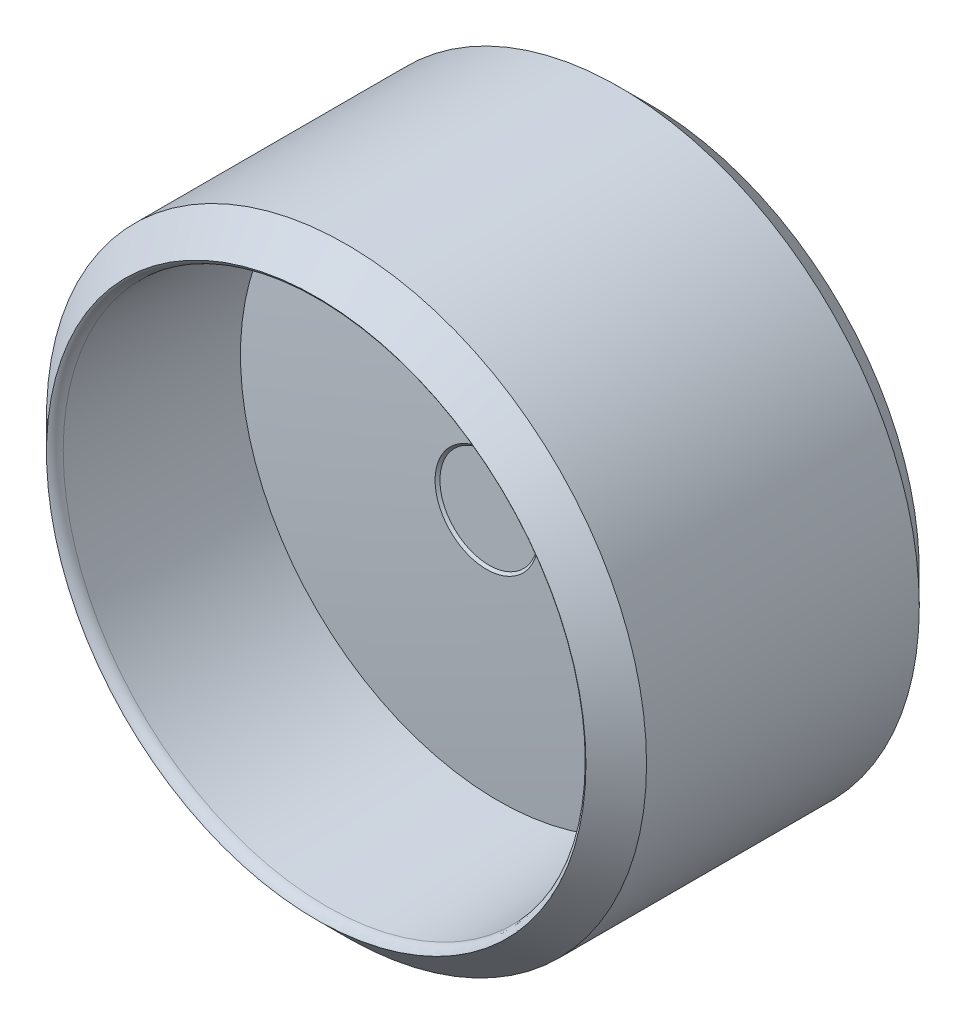
SolidWorks part; units mm, degrees
ref_plane "정면" through (0, 0, 0) normal (0, 0, 1) x (1, 0, 0)
ref_plane "윗면" through (0, 0, 0) normal (0, 1, 0) x (1, 0, 0)
ref_plane "우측면" through (0, 0, 0) normal (1, 0, 0) x (0, 0, -1)
sketch "스케치1" plane through (0, 0, 0) normal (0, 1, 0) x (1, 0, 0)
  line L0 (0, 0) -> (4, 0)
  line L1 (4, 0) -> (5.8947, 2)
  line L2 (5.8947, 2) -> (9.9, 2)
  line L3 (9.9, 2) -> (9.9, -9)
  line L4 (9.9, -9) -> (8.7, -9)
  line L5 (8.7, -9) -> (8.5, -3)
  line L6 (8.5, -3) -> (0, -3) construction
  line L7 (0, -3) -> (0, 0)
  line L8 (0, -3.4) -> (0, -3)
  arc A0 (8.5, -3) -> (0, -3.4) centre (-0.4238, 96.1172) cw
  dimension "D1" = 9.9
  dimension "D2" = 3
  dimension "D3" = 11
  dimension "D4" = 4
  dimension "D5" = 8.5
  dimension "D6" = 2
  dimension "D7" = 0.4
revolve "회전1" add sketch "스케치1" angle 360 about L7
chamfer "모따기1" distance 1 angle 45 2 edges at (9.9, 0, -2) (9.9, 0, 9)
fillet "필렛1" radius 0.4 2 edges at (5.8947, 0, -2) (8.7, 0, 9)
ref_plane "평면1" through (0, 0, 10) normal (0, 0, 1) x (1, 0, 0)
sketch "스케치2" plane through (0, 0, 10) normal (0, 0, 1) x (1, 0, 0)
  circle A0 centre (0, 0) radius 1.5
  dimension "D1" = 3
extrude "컷-돌출1" cut sketch "스케치2" against normal blind 6.7
chamfer "모따기2" distance 0.2 angle 45 1 edges at (-1.5, 0, 3.3823)
